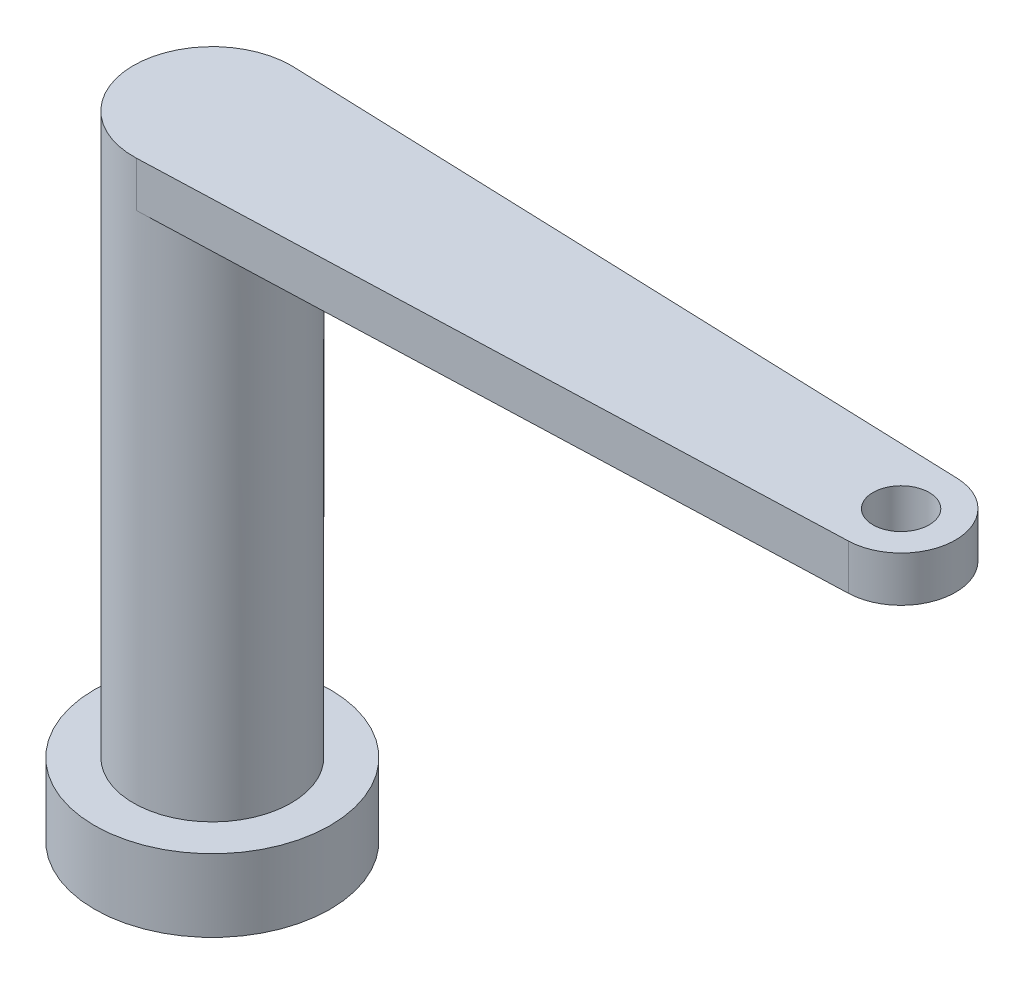
SolidWorks part; units mm, degrees
ref_plane "前视基准面" through (0, 0, 0) normal (0, 0, 1) x (1, 0, 0)
ref_plane "上视基准面" through (0, 0, 0) normal (0, 1, 0) x (1, 0, 0)
ref_plane "右视基准面" through (0, 0, 0) normal (1, 0, 0) x (0, 0, -1)
other "Configuration Table"
sketch "草图1" plane through (0, 0, 0) normal (0, 0, 1) x (1, 0, 0)
  line L0 (0, 0) -> (0, 56.4584) construction
  line L2 (3.4616, 5.8915) -> (1.4, 5.8915)
  line L3 (1.4, 5.8915) -> (1.4, 3.5)
  line L4 (1.4, 3.5) -> (2.5, 3.5)
  line L5 (2.5, 3.5) -> (2.5, 0)
  line L8 (4.35, 3.3915) -> (24, 3.3915)
  line L9 (24, 3.3915) -> (24, 5.8915)
  line L10 (24, 5.8915) -> (3.4616, 5.8915)
  line L11 (2.5, 0) -> (4.35, 0)
  line L12 (4.35, 0) -> (4.35, 3.3915)
  dimension "D1" = 2.5
  dimension "D2" = 2.8
  dimension "D3" = 3.5
  dimension "D4" = 3.3915
  dimension "D5" = 2.5
  dimension "D6" = 1.85
  dimension "D10" = 24
revolve "旋转1" add sketch "草图1" angle 360 about L0
sketch "草图2" plane through (0, 5.8915, 0) normal (0, 1, 0) x (1, 0, 0)
  circle A0 centre (0, 0) radius 16 construction
  circle A1 centre (0, 16) radius 1.5
  circle A2 centre (-16, 0) radius 1.5
  circle A3 centre (0, -16) radius 1.5
  circle A4 centre (16, 0) radius 1.5
  dimension "D1" = 32
  dimension "D2" = 3
  dimension "D3" = 3
  dimension "D4" = 3
  dimension "D5" = 3
extrude "切除-拉伸5" cut sketch "草图2" against normal blind 10 contours A2 | A3 | A4 | A1 region at (-16, 5.8915, 0) region at (0, 5.8915, 16) region at (16, 5.8915, 0)
sketch "草图3" plane through (0, 0, 0) normal (0, -1, 0) x (1, 0, 0)
  circle A0 centre (0, 0) radius 2.5
  dimension "D1" = 5
extrude "凸台-拉伸1" add sketch "草图3" along normal blind 20 separate body
sketch "草图4" plane through (0, -20, 0) normal (0, -1, 0) x (1, 0, 0)
  circle A0 centre (0, 0) radius 1.85
  dimension "D1" = 3.7
extrude "凸台-拉伸2" add sketch "草图4" along normal blind 5
extrude "凸台-拉伸3" add sketch "草图3<2>" against normal up to surface (5.8915 mm away) up to face at (-16, 5.8915, 1.5)
sketch "草图3<2>" plane through (0, 0, 0) normal (0, -1, 0) x (1, 0, 0) same geometry as "草图3"
sketch "草图5" plane through (0, 0, 0) normal (0, -1, 0) x (1, 0, 0)
  circle A0 centre (0, 0) radius 4.35
  dimension "D1" = 8.7
extrude "凸台-拉伸4" add sketch "草图5" along normal through all
sketch "草图6" plane through (0, -25, 0) normal (0, -1, 0) x (1, 0, 0)
  circle A0 centre (0, 0) radius 6.5
  dimension "D1" = 13
extrude "凸台-拉伸5" add sketch "草图6" along normal blind 4
sketch "草图7" plane through (0, 5.8915, 0) normal (0, 1, 0) x (1, 0, 0)
  line L0 (0.367, 4.3345) -> (16.2531, 2.9893)
  line L1 (0.367, -4.3345) -> (16.2531, -2.9893)
  arc A1 (16.2531, -2.9893) -> (16.2531, 2.9893) centre (16, 0) ccw
  arc A3 (0.367, 4.3345) -> (0.367, -4.3345) centre (0, 0) ccw
  dimension "D1" = 8.7
  dimension "D2" = 6
extrude "切除-拉伸6" cut sketch "草图7" against normal blind 5 flip side to cut
sketch "草图8" plane through (0, 5.8915, 0) normal (0, 1, 0) x (1, 0, 0)
  line L0 (0.1545, 4.3473) -> (38.1066, 2.9981)
  line L1 (0.1545, -4.3473) -> (38.1066, -2.9981)
  line L2 (16.2531, 2.9893) -> (0.367, 4.3345)
  line L3 (0.367, -4.3345) -> (16.2531, -2.9893)
  arc A0 (38.1066, -2.9981) -> (38.1066, 2.9981) centre (38, 0) ccw
  circle A1 centre (38, 0) radius 1.55
  arc A3 (16.2531, -2.9893) -> (16.2531, 2.9893) centre (16, 0) ccw
  arc A6 (0.367, 4.3345) -> (0.367, -4.3345) centre (0, 0) ccw construction
  circle A7 centre (0, 0) radius 4.35 construction
  arc A10 (0.367, 4.3345) -> (0.367, -4.3345) centre (0, 0) ccw
  arc A11 (0.1545, 4.3473) -> (0.1545, -4.3473) centre (0, 0) ccw
  dimension "D2" = 38
  dimension "D3" = 3.1
  dimension "D4" = 3
  dimension "D1" = 0
extrude "凸台-拉伸6" add sketch "草图8" against normal blind 2.5
